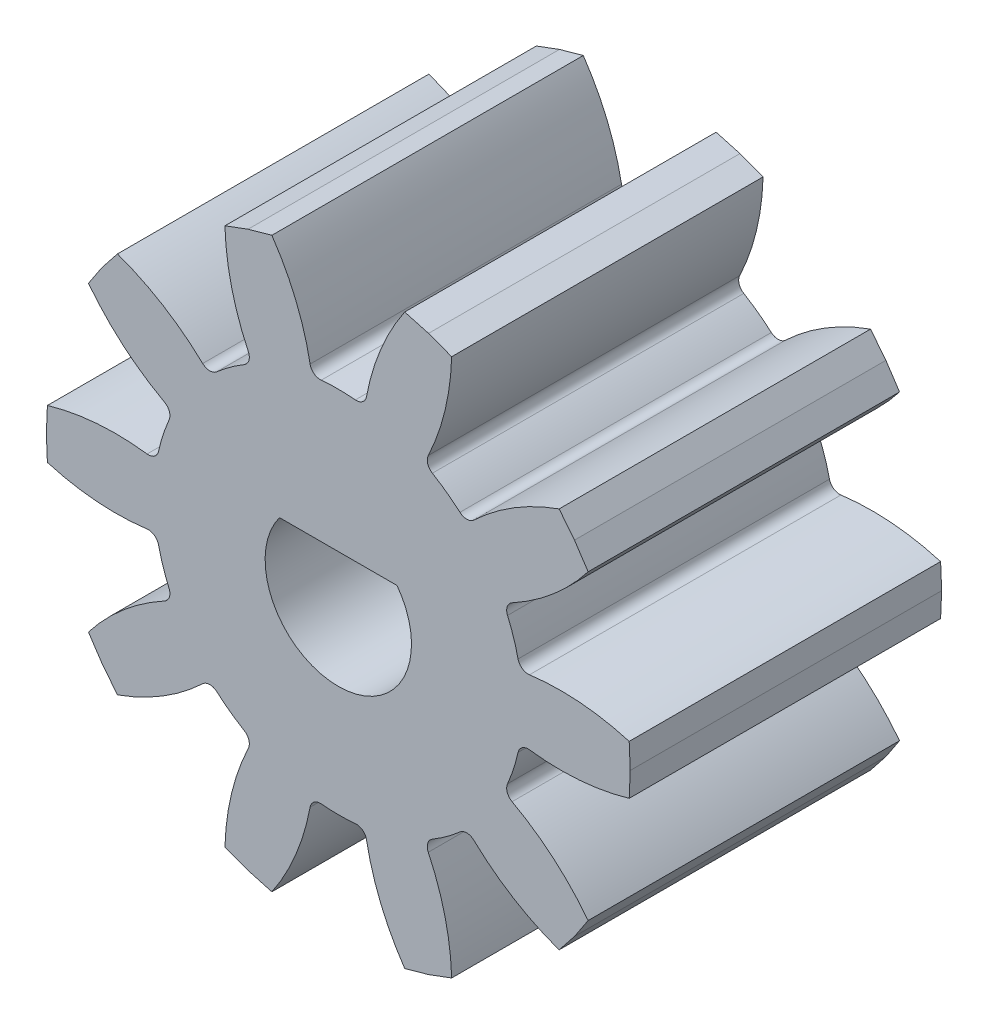
SolidWorks part; units mm, degrees
ref_plane "Front Plane" through (0, 0, 0) normal (0, 0, 1) x (1, 0, 0)
ref_plane "Top Plane" through (0, 0, 0) normal (0, 1, 0) x (1, 0, 0)
ref_plane "Right Plane" through (0, 0, 0) normal (1, 0, 0) x (0, 0, -1)
sketch "Sketch1" plane through (0, 0, 0) normal (0, 0, 1) x (1, 0, 0)
  line L0 (0, 0) -> (74.4139, 0) construction
  line L1 (0, 0) -> (5.6279, 1.8286) construction
  line L2 (0, 0) -> (74.4139, 12.7198) construction
  line L3 (0, 0) -> (74.4139, 6.3141) construction
  line L4 (9.3414, 0.7926) -> (9.375, 0)
  line L5 (0, 0) -> (5.6279, -1.8286) construction
  line L6 (0, 0) -> (5.6279, 1.8286)
  line L7 (0, 0) -> (5.6279, -1.8286) construction
  line L8 (0, 0) -> (5.6279, -1.8286)
  line L9 (9.3414, -0.7926) -> (9.375, 0)
  circle A0 centre (0, 0) radius 9.375 construction
  circle A1 centre (0, 0) radius 7.8125 construction
  circle A2 centre (0, 0) radius 5.9175 construction
  arc A3 (5.8329, 0.997) -> (9.3414, 0.7926) centre (7.1457, -6.6831) cw
  arc A4 (5.8329, 0.997) -> (5.6279, 1.8286) centre (0, 0) ccw
  arc A5 (5.8329, -0.997) -> (5.6279, -1.8286) centre (0, 0) cw
  arc A6 (5.8329, -0.997) -> (9.3414, -0.7926) centre (7.1457, 6.6831) ccw
  dimension "D1" = 18.75
  dimension "D2" = 1.5625
  dimension "D3" = 1.895
  dimension "D4" = 18
  dimension "D5" = 9.7
  dimension "D6" = 4.85
extrude "Boss-Extrude1" add sketch "Sketch1" along normal blind 10
fillet "Fillet1" radius 0.3325 2 edges at (5.8329, 0.997, 5) (5.8329, -0.997, 5)
pattern_circular "CirPattern1" count 10 over 360 about axis through (0, 0, 10) along (0, 0, -1) of "Boss-Extrude1", "Fillet1"
sketch "Sketch2" plane through (0, 0, 0) normal (0, 0, -1) x (-1, 0, 0)
  line L0 (-1.8875, 1.4) -> (1.8875, 1.4)
  arc A0 (-1.8875, 1.4) -> (1.8875, 1.4) centre (0, 0) ccw
  dimension "D1" = 4.7
  dimension "D2" = 1.4
extrude "Cut-Extrude1" cut sketch "Sketch2" against normal up to next
